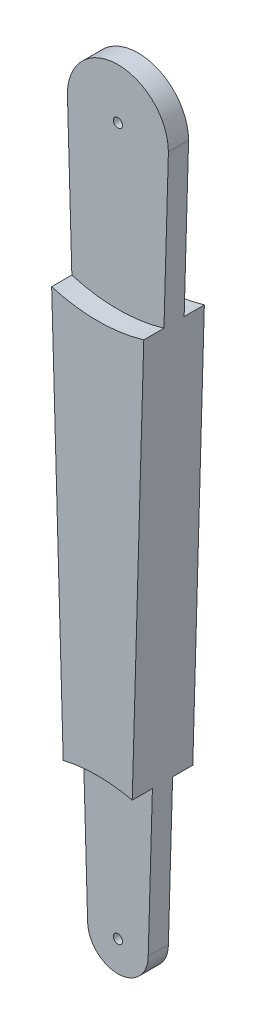
SolidWorks part; units mm, degrees
ref_plane "Front Plane" through (0, 0, 0) normal (0, 0, 1) x (1, 0, 0)
ref_plane "Top Plane" through (0, 0, 0) normal (0, 1, 0) x (1, 0, 0)
ref_plane "Right Plane" through (0, 0, 0) normal (1, 0, 0) x (0, 0, -1)
sketch "Sketch2" plane through (0, 0, 0) normal (0, 0, 1) x (1, 0, 0)
  line L1 (15, -350) -> (25, 0)
  line L2 (-15, -350) -> (-25, 0)
  line L3 (0, -350) -> (0, -397.2479)
  line L4 (0, -320) -> (0, -350)
  arc A2 (25, 0) -> (-25, 0) centre (0, 0) ccw
  arc A4 (-15, -350) -> (15, -350) centre (0, -350) ccw
  dimension "D1" = 350
  dimension "D2" = 50
  dimension "D3" = 15
extrude "Boss-Extrude1" add sketch "Sketch2" along normal blind 30 contours L2 A4 L1 A2 region at (0, -153.9837, 0)
sketch "Sketch3" plane through (0, 0, 30) normal (0, 0, 1) x (1, 0, 0)
  circle A0 centre (0, 0) radius 80
  dimension "D1" = 160
extrude "Cut-Extrude1" cut sketch "Sketch3" against normal blind 10
ref_plane "Plane1" through (0, 0, 15) normal (0, 0, 1) x (1, 0, 0)
mirror "Mirror1" about plane through (0, 0, 15) normal (0, 0, 1) of "Cut-Extrude1"
sketch "Sketch4" plane through (0, 0, 20) normal (0, 0, 1) x (1, 0, 0)
  circle A0 centre (0, 0) radius 2.25
  dimension "D1" = 4.5
extrude "Cut-Extrude2" cut sketch "Sketch4" against normal blind 10
sketch "Sketch5" plane through (0, 0, 0) normal (0, 0, -1) x (-1, 0, 0)
  circle A0 centre (0, -350) radius 75
  dimension "D1" = 150
extrude "Cut-Extrude3" cut sketch "Sketch5" against normal blind 10
mirror "Mirror2" about plane through (0, 0, 15) normal (0, 0, 1) of "Cut-Extrude3"
sketch "Sketch6" plane through (0, 0, 10) normal (0, 0, -1) x (-1, 0, 0)
  circle A0 centre (0, -350) radius 2.25
  dimension "D1" = 4.5
extrude "Cut-Extrude4" cut sketch "Sketch6" against normal blind 10
